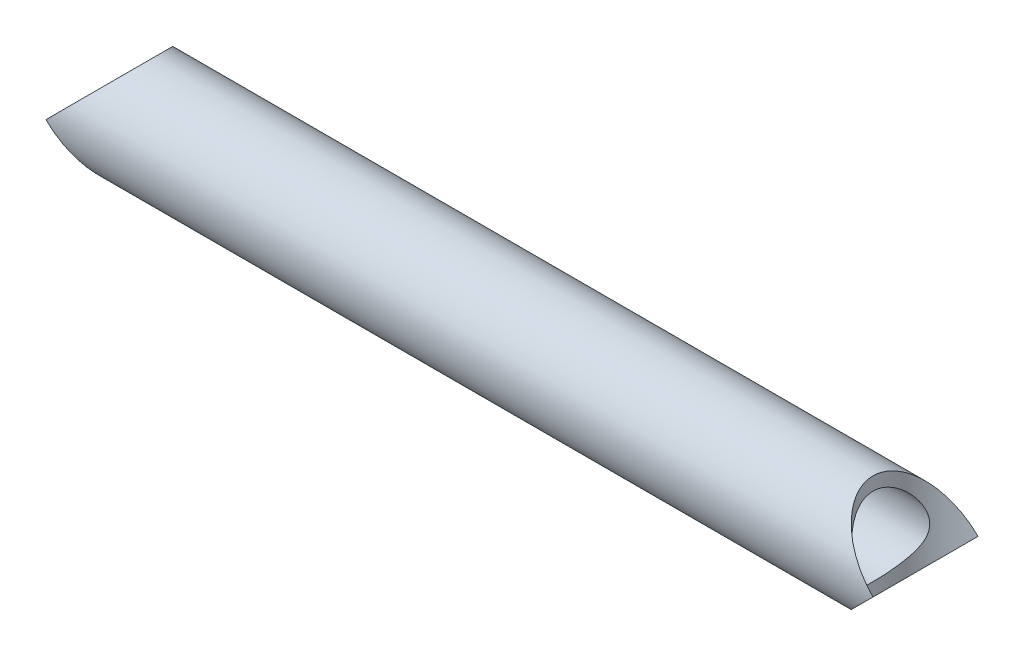
SolidWorks part; units mm, degrees
ref_plane "Front Plane" through (0, 0, 0) normal (0, 0, 1) x (1, 0, 0)
ref_plane "Top Plane" through (0, 0, 0) normal (0, 1, 0) x (1, 0, 0)
ref_plane "Right Plane" through (0, 0, 0) normal (1, 0, 0) x (0, 0, -1)
sketch "Sketch1" plane through (0, 0, 0) normal (1, 0, 0) x (0, 0, -1)
  circle A0 centre (0, 0) radius 9.525
  circle A1 centre (0, 0) radius 7.112
  dimension "D1" = 19.05
  dimension "D2" = 2.413
extrude "Boss-Extrude1" add sketch "Sketch1" along normal blind 150
sketch "Sketch2" plane through (0, 0, 0) normal (0, 1, 0) x (1, 0, 0)
  line L0 (150, -9.525) -> (150, 9.525) construction
  circle A0 centre (0, 0) radius 9.525
  circle A1 centre (150, 0) radius 9.525
  dimension "D1" = 19.05
extrude "Cut-Extrude1" cut sketch "Sketch2" against normal blind 25 and the other way blind 25
